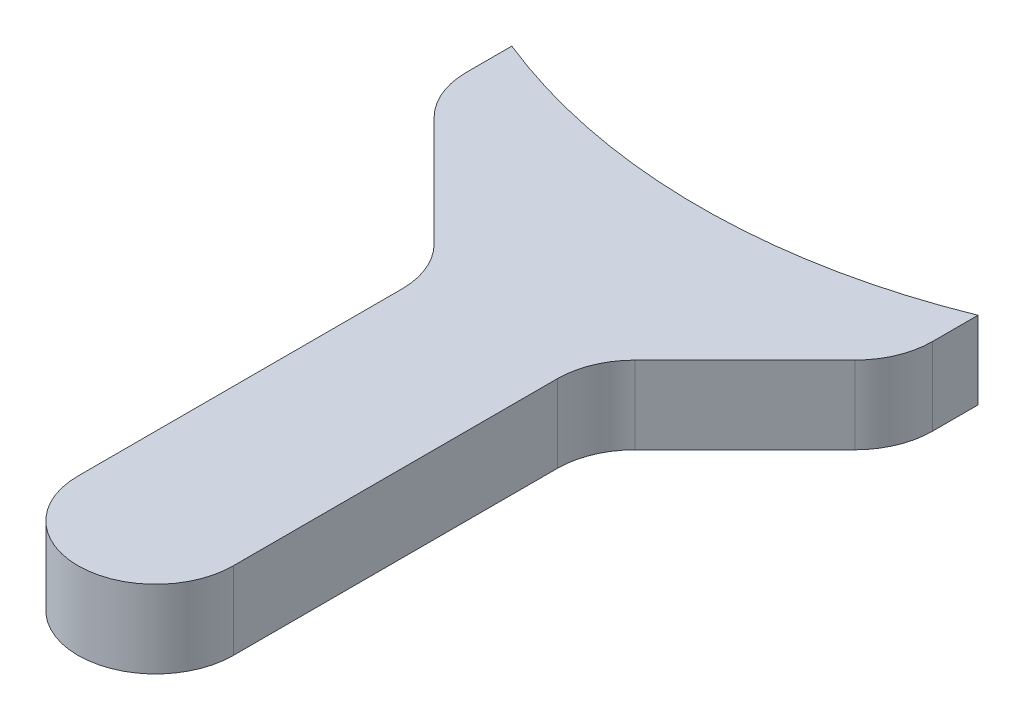
SolidWorks part; units mm, degrees
ref_plane "Front Plane" through (0, 0, 0) normal (0, 0, 1) x (1, 0, 0)
ref_plane "Top Plane" through (0, 0, 0) normal (0, 1, 0) x (1, 0, 0)
ref_plane "Right Plane" through (0, 0, 0) normal (1, 0, 0) x (0, 0, -1)
sketch "Sketch1" plane through (0, 0, 0) normal (0, 1, 0) x (1, 0, 0)
  line L0 (0, -101.6) -> (0, -203.2)
  line L1 (0, -203.2) -> (12.7, -203.2)
  line L2 (12.7, -203.2) -> (12.7, -132.2857)
  line L3 (12.7, -132.2857) -> (38.1, -106.8857)
  line L4 (38.1, -106.8857) -> (38.1, -94.1857)
  line L5 (0, 0) -> (0, -101.6) construction
  arc A0 (0, -101.6) -> (38.1, -94.1857) centre (0, 0) ccw
  dimension "D1" = 203.2
  dimension "D2" = 38.1
  dimension "D3" = 12.7
  dimension "D4" = 12.7
  dimension "D5" = 45
  dimension "D6" = 101.6
extrude "Boss-Extrude1" add sketch "Sketch1" along normal blind 12.7
fillet "Fillet1" radius 12.7 3 edges at (38.1, 6.35, 106.8857) (12.7, 6.35, 132.2857) (12.7, 6.35, 203.2)
mirror "Mirror1" about plane through (0, 12.7, 101.6) normal (1, 0, 0) of bodies 101
